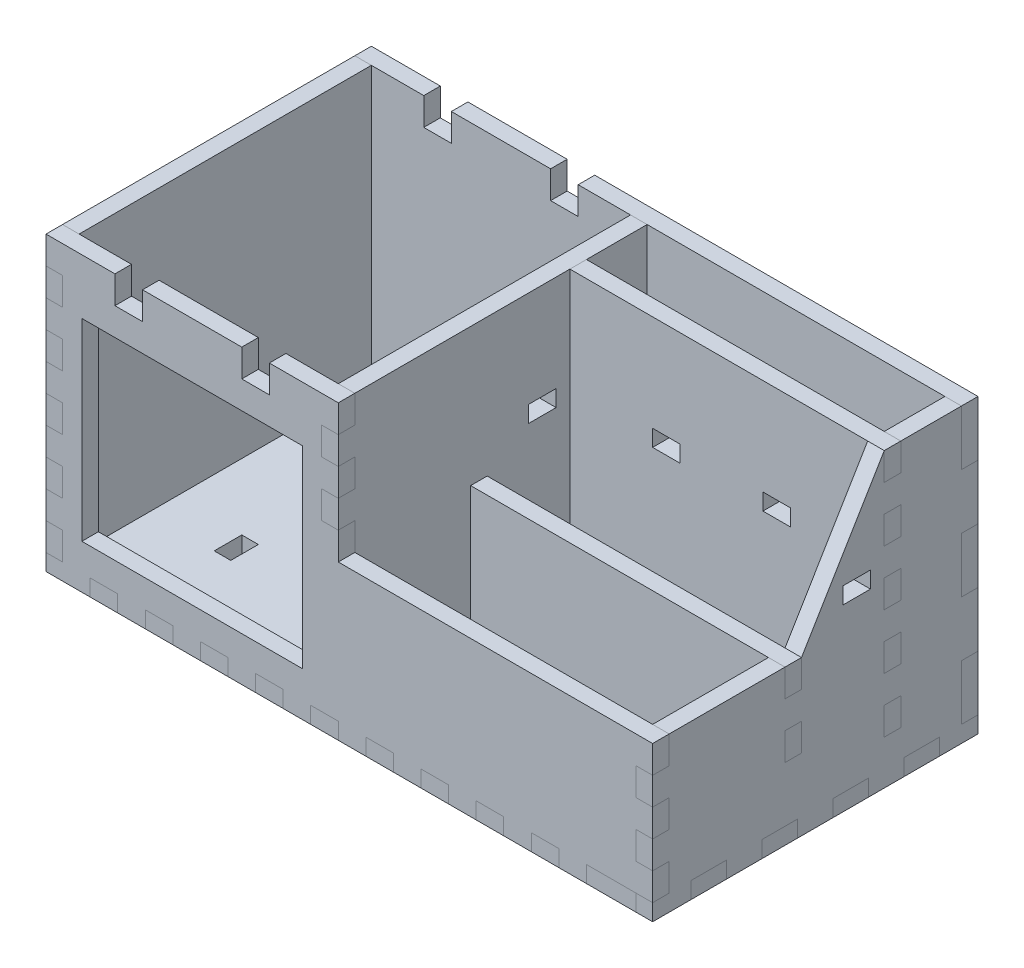
SolidWorks part; units mm, degrees
ref_plane "Front Plane" through (0, 0, 0) normal (0, 0, 1) x (1, 0, 0)
ref_plane "Top Plane" through (0, 0, 0) normal (0, 1, 0) x (1, 0, 0)
ref_plane "Right Plane" through (0, 0, 0) normal (1, 0, 0) x (0, 0, -1)
sketch "Sketch1" plane through (0, 0, 0) normal (0, 0, 1) x (1, 0, 0)
  line L0 (6, 106) -> (6, 0) construction
  line L1 (0, 0) -> (220, 0) construction
  line L2 (0, 0) -> (0, 106) construction
  line L3 (0, 106) -> (220, 106) construction
  line L4 (220, 0) -> (220, 106) construction
  line L5 (106, 106) -> (106, 0) construction
  line L6 (0, 6) -> (220, 6) construction
  line L7 (0, 56) -> (220, 56) construction
  line L8 (106, 106) -> (81, 106)
  line L9 (220, 56) -> (106, 56)
  line L10 (0, 106) -> (0, 96)
  line L11 (0, 96) -> (6, 96)
  line L12 (6, 96) -> (6, 86)
  line L13 (6, 86) -> (0, 86)
  line L14 (6, 66) -> (0, 66)
  line L15 (6, 76) -> (6, 66)
  line L16 (0, 76) -> (6, 76)
  line L17 (0, 86) -> (0, 76)
  line L18 (6, 46) -> (0, 46)
  line L19 (6, 56) -> (6, 46)
  line L20 (0, 56) -> (6, 56)
  line L21 (0, 66) -> (0, 56)
  line L22 (6, 26) -> (0, 26)
  line L23 (6, 36) -> (6, 26)
  line L24 (0, 36) -> (6, 36)
  line L25 (0, 46) -> (0, 36)
  line L26 (6, 6) -> (0, 6)
  line L27 (6, 16) -> (6, 6)
  line L28 (0, 16) -> (6, 16)
  line L29 (0, 26) -> (0, 16)
  line L30 (6, 0) -> (16, 0)
  line L31 (16, 0) -> (16, 6)
  line L32 (16, 6) -> (26, 6)
  line L33 (26, 6) -> (26, 0)
  line L34 (26, 0) -> (36, 0)
  line L35 (36, 0) -> (36, 6)
  line L36 (36, 6) -> (46, 6)
  line L37 (46, 6) -> (46, 0)
  line L38 (46, 0) -> (56, 0)
  line L39 (56, 0) -> (56, 6)
  line L40 (56, 6) -> (66, 6)
  line L41 (66, 6) -> (66, 0)
  line L42 (66, 0) -> (76, 0)
  line L43 (76, 0) -> (76, 6)
  line L44 (76, 6) -> (86, 6)
  line L45 (86, 6) -> (86, 0)
  line L46 (86, 0) -> (96, 0)
  line L47 (96, 0) -> (96, 6)
  line L48 (96, 6) -> (106, 6)
  line L49 (106, 6) -> (106, 0)
  line L50 (106, 0) -> (116, 0)
  line L51 (116, 0) -> (116, 6)
  line L52 (116, 6) -> (126, 6)
  line L53 (126, 6) -> (126, 0)
  line L54 (126, 0) -> (136, 0)
  line L55 (136, 0) -> (136, 6)
  line L56 (136, 6) -> (146, 6)
  line L57 (146, 6) -> (146, 0)
  line L58 (146, 0) -> (156, 0)
  line L59 (156, 0) -> (156, 6)
  line L60 (156, 6) -> (166, 6)
  line L61 (166, 6) -> (166, 0)
  line L62 (166, 0) -> (176, 0)
  line L63 (176, 0) -> (176, 6)
  line L64 (176, 6) -> (186, 6)
  line L65 (186, 6) -> (186, 0)
  line L66 (186, 0) -> (196, 0)
  line L67 (196, 0) -> (196, 6)
  line L68 (196, 6) -> (206, 6)
  line L69 (100, 106) -> (100, 6) construction
  line L70 (6, 0) -> (0, 0)
  line L71 (0, 0) -> (0, 6)
  line L72 (214, 56) -> (214, 0) construction
  line L73 (220, 56) -> (220, 46)
  line L74 (220, 46) -> (214, 46)
  line L75 (214, 46) -> (214, 36)
  line L76 (214, 36) -> (220, 36)
  line L77 (220, 36) -> (220, 26)
  line L78 (220, 26) -> (214, 26)
  line L79 (214, 26) -> (214, 16)
  line L80 (214, 16) -> (220, 16)
  line L81 (220, 16) -> (220, 6)
  line L82 (220, 6) -> (206, 6)
  line L83 (106, 106) -> (106, 96)
  line L84 (206, 6) -> (206, 0) [skipped]
  line L85 (106, 96) -> (100, 96)
  line L86 (100, 96) -> (100, 86)
  line L87 (100, 86) -> (106, 86)
  line L88 (106, 86) -> (106, 76)
  line L89 (106, 76) -> (100, 76)
  line L90 (100, 76) -> (100, 66)
  line L91 (100, 66) -> (106, 66)
  line L92 (106, 66) -> (106, 56)
  line L93 (25, 106) -> (0, 106)
  line L94 (35, 106) -> (25, 106) construction
  line L95 (71, 106) -> (35, 106)
  line L96 (81, 106) -> (71, 106) construction
  line L97 (0, 96) -> (106, 96) construction
  line L98 (25, 106) -> (25, 96)
  line L99 (25, 96) -> (35, 96)
  line L100 (35, 96) -> (35, 106)
  line L101 (71, 106) -> (71, 96)
  line L102 (71, 96) -> (81, 96)
  line L103 (81, 96) -> (81, 106)
  line L104 (53, 106) -> (53, 0) construction
  line L105 (13, 86) -> (93, 86)
  line L106 (13, 86) -> (13, 16)
  line L107 (13, 16) -> (93, 16)
  line L108 (93, 86) -> (93, 16)
  point P111 (53, 86)
  dimension "D1" = 6
  dimension "D2" = 220
  dimension "D3" = 106
  dimension "D4" = 6
  dimension "D5" = 106
  dimension "D6" = 56
  dimension "D7" = 10
  dimension "D10" = 6
  dimension "D11" = 6
  dimension "D12" = 10
  dimension "D13" = 10
  dimension "D14" = 25
  dimension "D15" = 25
  dimension "D16" = 10
  dimension "D17" = 70
  dimension "D18" = 10
  dimension "D19" = 80
  dimension "D8" = 5
  dimension "D9" = 10
extrude "Boss-Extrude1" add sketch "Sketch1" along normal blind 6
sketch "Sketch2" plane through (0, 0, 0) normal (0, 1, 0) x (1, 0, 0)
  line L0 (0, -6) -> (16, -6) construction
  line L1 (0, -6) -> (220, -6)
  line L2 (0, -6) -> (0, 112)
  line L3 (0, 112) -> (220, 112)
  line L4 (220, -6) -> (220, 112)
  line L5 (0, -6) -> (0, 0) construction
  dimension "D1" = 220
  dimension "D2" = 118
extrude "Boss-Extrude2" add sketch "Sketch2" along normal blind 6 separate body
sketch "Sketch5" plane through (0, 0, 0) normal (1, 0, 0) x (0, 0, -1)
  line L0 (-6, 26) -> (-6, 16) construction
  line L1 (-6, 106) -> (112, 106)
  line L2 (-6, 106) -> (-6, 6)
  line L3 (-6, 0) -> (112, 0) construction
  line L4 (112, 106) -> (112, 6)
  line L5 (112, 0) -> (-6, 0) construction
  line L6 (-6, 6) -> (0, 6)
  line L7 (0, 6) -> (0, 0)
  line L8 (0, 0) -> (11.7778, 0)
  line L9 (11.7778, 0) -> (11.7778, 6)
  line L10 (-6, 6) -> (112, 6) construction
  line L11 (11.7778, 6) -> (23.5556, 6)
  line L12 (23.5556, 6) -> (23.5556, 0)
  line L13 (23.5556, 0) -> (35.3333, 0)
  line L14 (35.3333, 0) -> (35.3333, 6)
  line L15 (35.3333, 6) -> (47.1111, 6)
  line L16 (47.1111, 6) -> (47.1111, 0)
  line L17 (47.1111, 0) -> (58.8889, 0)
  line L18 (58.8889, 0) -> (58.8889, 6)
  line L19 (58.8889, 6) -> (70.6667, 6)
  line L20 (70.6667, 6) -> (70.6667, 0)
  line L21 (70.6667, 0) -> (82.4444, 0)
  line L22 (82.4444, 0) -> (82.4444, 6)
  line L23 (82.4444, 6) -> (94.2222, 6)
  line L24 (94.2222, 6) -> (94.2222, 0)
  line L25 (94.2222, 0) -> (106, 0)
  line L26 (106, 0) -> (106, 6) construction
  line L27 (106, 6) -> (112, 6) construction
  line L28 (-6, 6) -> (-6, 0) construction
  line L29 (112, 6) -> (112, 0)
  line L30 (112, 0) -> (106, 0)
  dimension "D1" = 118
  dimension "D2" = 106
  dimension "D4" = 6
  dimension "D5" = 6
extrude "Boss-Extrude9" add sketch "Sketch5" along normal blind 6 separate body
sketch "Sketch11" plane through (214, 0, 0) normal (1, 0, 0) x (0, 0, -1)
  line L0 (-6, 0) -> (0, 0)
  line L1 (-6, 0) -> (112, 0) construction
  line L2 (-6, 0) -> (-6, 5.9466)
  line L3 (-6, 106) -> (78, 106) construction
  line L4 (112, 0) -> (112, 106)
  line L5 (0, 0) -> (8, 0)
  line L6 (98, 0) -> (112, 0)
  line L7 (8, 0) -> (8, 6)
  line L8 (8, 6) -> (20.8571, 6)
  line L9 (20.8571, 6) -> (20.8571, 0)
  line L10 (-6, 6) -> (112, 6) construction
  line L11 (0, 6) -> (0, 0) construction
  line L12 (-6, 5.9466) -> (-6, 56)
  line L13 (20.8571, 0) -> (33.7143, 0)
  line L14 (33.7143, 0) -> (33.7143, 6)
  line L15 (33.7143, 6) -> (46.5714, 6)
  line L16 (46.5714, 6) -> (46.5714, 0)
  line L17 (46.5714, 0) -> (59.4286, 0)
  line L18 (59.4286, 0) -> (59.4286, 6)
  line L19 (59.4286, 6) -> (72.2857, 6)
  line L20 (72.2857, 6) -> (72.2857, 0)
  line L21 (72.2857, 0) -> (85.1429, 0)
  line L22 (85.1429, 0) -> (85.1429, 6)
  line L23 (85.1429, 6) -> (98, 6)
  line L24 (98, 6) -> (98, 0)
  line L25 (-6, 46) -> (-6, 56) construction
  line L28 (-6, 56) -> (-6, 106) construction
  line L29 (78, 106) -> (112, 106)
  line L30 (78, 106) -> (48, 56)
  line L31 (-6, 56) -> (48, 56)
  line L32 (-6, 56) -> (0, 56) construction
  line L34 (112, 0) -> (112, 6) construction
  dimension "D1" = 106
  dimension "D2" = 118
  dimension "D3" = 6
  dimension "D4" = 8
  dimension "D5" = 14
  dimension "D6" = 34
  dimension "D7" = 54
extrude "Boss-Extrude11" add sketch "Sketch11" along normal blind 6 separate body
sketch "Sketch15" plane through (0, 0, -112) normal (0, 0, -1) x (-1, 0, 0)
  line L0 (-214, 106) -> (-214, 0) construction
  line L1 (-220, 0) -> (-214, 0) construction
  line L2 (-220, 0) -> (-220, 106) construction
  line L3 (-220, 106) -> (-81, 106)
  line L4 (0, 0) -> (0, 106) construction
  line L5 (-6, 106) -> (-6, 0) construction
  line L6 (-220, 106) -> (-220, 86)
  line L7 (-220, 86) -> (-214, 86)
  line L8 (-214, 86) -> (-214, 66)
  line L9 (-214, 66) -> (-220, 66)
  line L10 (-220, 66) -> (-220, 46)
  line L11 (-220, 46) -> (-214, 46)
  line L12 (-214, 46) -> (-214, 26)
  line L13 (-214, 26) -> (-220, 26)
  line L14 (-220, 26) -> (-220, 6)
  line L15 (-220, 6) -> (-214, 6) construction
  line L16 (-214, 6) -> (-214, 0)
  line L17 (-214, 0) -> (-6, 0) construction
  line L18 (-214, 6) -> (-220, 6)
  line L19 (0, 106) -> (0, 86)
  line L20 (0, 86) -> (-6, 86)
  line L21 (-6, 86) -> (-6, 66)
  line L22 (-6, 66) -> (0, 66)
  line L23 (0, 66) -> (0, 46)
  line L24 (0, 46) -> (-6, 46)
  line L25 (-6, 46) -> (-6, 26)
  line L26 (-6, 26) -> (0, 26)
  line L27 (0, 26) -> (0, 6)
  line L28 (0, 6) -> (-6, 6)
  line L29 (-6, 6) -> (-6, 0)
  line L30 (-6, 0) -> (0, 0) construction
  line L31 (-214, 0) -> (-195.0909, 0)
  line L32 (-195.0909, 0) -> (-195.0909, 6)
  line L33 (-220, 6) -> (0, 6) construction
  line L34 (-195.0909, 6) -> (-176.1818, 6)
  line L35 (-176.1818, 6) -> (-176.1818, 0)
  line L36 (-176.1818, 0) -> (-157.2727, 0)
  line L37 (-157.2727, 0) -> (-157.2727, 6)
  line L38 (-157.2727, 6) -> (-138.3636, 6)
  line L39 (-138.3636, 6) -> (-138.3636, 0)
  line L40 (-138.3636, 0) -> (-119.4545, 0)
  line L41 (-119.4545, 0) -> (-119.4545, 6)
  line L42 (-119.4545, 6) -> (-100.5455, 6)
  line L43 (-100.5455, 6) -> (-100.5455, 0)
  line L44 (-100.5455, 0) -> (-81.6364, 0)
  line L45 (-81.6364, 0) -> (-81.6364, 6)
  line L46 (-81.6364, 6) -> (-62.7273, 6)
  line L47 (-62.7273, 6) -> (-62.7273, 0)
  line L48 (-62.7273, 0) -> (-43.8182, 0)
  line L49 (-43.8182, 0) -> (-43.8182, 6)
  line L50 (-43.8182, 6) -> (-24.9091, 6)
  line L51 (-24.9091, 6) -> (-24.9091, 0)
  line L52 (-24.9091, 0) -> (-6, 0)
  line L53 (-81, 106) -> (-81, 96)
  line L54 (-81, 96) -> (-71, 96)
  line L55 (-81, 96) -> (-71, 96) construction
  line L56 (-71, 96) -> (-71, 106)
  line L57 (-81, 106) -> (-71, 106) construction
  line L58 (-71, 106) -> (-35, 106)
  line L59 (-35, 106) -> (-35, 96)
  line L60 (-35, 96) -> (-25, 96)
  line L61 (-25, 96) -> (-25, 106) construction
  line L62 (-35, 96) -> (-25, 96) construction
  line L63 (-25, 96) -> (-25, 106)
  line L64 (-35, 106) -> (-25, 106) construction
  line L65 (-25, 106) -> (0, 106)
  dimension "D1" = 220
  dimension "D2" = 106
  dimension "D3" = 6
  dimension "D4" = 6
  dimension "D5" = 6
extrude "Boss-Extrude13" add sketch "Sketch15" against normal blind 6 separate body
sketch "Sketch22" plane through (100, 0, 0) normal (1, 0, 0) x (0, 0, -1)
  line L0 (-6, 86) -> (-6, 96) construction
  line L1 (-6, 106) -> (106, 106)
  line L2 (-6, 106) -> (-6, 6)
  line L3 (-6, 6) -> (19, 6)
  line L4 (112, 106) -> (112, 6) construction
  line L5 (106, 106) -> (112, 106) construction
  line L6 (106, 106) -> (106, 6) construction
  line L7 (106, 106) -> (106, 86)
  line L8 (106, 86) -> (112, 86)
  line L9 (112, 86) -> (112, 66)
  line L10 (112, 66) -> (106, 66)
  line L11 (106, 66) -> (106, 46)
  line L12 (106, 46) -> (112, 46)
  line L13 (112, 46) -> (112, 26)
  line L14 (112, 26) -> (106, 26)
  line L15 (106, 26) -> (106, 6)
  line L16 (106, 6) -> (112, 6) construction
  line L17 (-6, 0) -> (94, 0) construction
  line L18 (19, 6) -> (34, 6) construction
  line L19 (34, 6) -> (59, 6)
  line L20 (59, 6) -> (74, 6) construction
  line L21 (74, 6) -> (106, 6)
  line L22 (19, 6) -> (19, 0)
  line L23 (19, 0) -> (34, 0)
  line L24 (34, 0) -> (34, 6)
  line L25 (59, 6) -> (59, 0)
  line L26 (59, 0) -> (74, 0)
  line L27 (74, 0) -> (74, 6)
  dimension "D1" = 118
  dimension "D2" = 100
  dimension "D3" = 6
  dimension "D4" = 15
  dimension "D5" = 25
  dimension "D6" = 25
extrude "Boss-Extrude14" add sketch "Sketch22" along normal blind 6 separate body
sketch "Sketch19" plane through (0, 0, -112) normal (0, 0, -1) x (-1, 0, 0)
  line L44 (0, 86) -> (0, 106)
  line L45 (-81, 106) -> (-220, 106)
  line L46 (-220, 106) -> (-220, 86)
  line L47 (-220, 86) -> (-214, 86)
  line L48 (-214, 86) -> (-214, 66)
  line L49 (-214, 66) -> (-220, 66)
  line L50 (-220, 66) -> (-220, 46)
  line L51 (-220, 46) -> (-214, 46)
  line L52 (-214, 46) -> (-214, 26)
  line L53 (-214, 26) -> (-220, 26)
  line L54 (-220, 26) -> (-220, 6)
  line L55 (-220, 6) -> (-214, 6)
  line L56 (-214, 6) -> (-214, 0)
  line L57 (-214, 0) -> (-195.0909, 0)
  line L58 (-195.0909, 0) -> (-195.0909, 6)
  line L59 (-195.0909, 6) -> (-176.1818, 6)
  line L60 (-176.1818, 6) -> (-176.1818, 0)
  line L61 (-176.1818, 0) -> (-157.2727, 0)
  line L62 (-157.2727, 0) -> (-157.2727, 6)
  line L63 (-157.2727, 6) -> (-138.3636, 6)
  line L64 (-138.3636, 6) -> (-138.3636, 0)
  line L65 (-138.3636, 0) -> (-119.4545, 0)
  line L66 (-119.4545, 0) -> (-119.4545, 6)
  line L67 (-119.4545, 6) -> (-100.5455, 6)
  line L68 (-100.5455, 6) -> (-100.5455, 0)
  line L69 (-100.5455, 0) -> (-81.6364, 0)
  line L70 (-81.6364, 0) -> (-81.6364, 6)
  line L71 (-81.6364, 6) -> (-62.7273, 6)
  line L72 (-62.7273, 6) -> (-62.7273, 0)
  line L73 (-62.7273, 0) -> (-43.8182, 0)
  line L74 (-43.8182, 0) -> (-43.8182, 6)
  line L75 (-43.8182, 6) -> (-24.9091, 6)
  line L76 (-24.9091, 6) -> (-24.9091, 0)
  line L77 (-24.9091, 0) -> (-6, 0)
  line L78 (-6, 0) -> (-6, 6)
  line L79 (-6, 6) -> (0, 6)
  line L80 (0, 6) -> (0, 26)
  line L81 (0, 26) -> (-6, 26)
  line L82 (-6, 26) -> (-6, 46)
  line L83 (-6, 46) -> (0, 46)
  line L84 (0, 46) -> (0, 66)
  line L85 (0, 66) -> (-6, 66)
  line L86 (-6, 66) -> (-6, 86)
  line L87 (-6, 86) -> (0, 86)
  line L88 (0, 86) -> (0, 106)
  line L89 (-81, 106) -> (-220, 106)
  line L90 (-220, 106) -> (-220, 86)
  line L91 (-220, 86) -> (-214, 86)
  line L92 (-214, 86) -> (-214, 66)
  line L93 (-214, 66) -> (-220, 66)
  line L94 (-220, 66) -> (-220, 46)
  line L95 (-220, 46) -> (-214, 46)
  line L96 (-214, 46) -> (-214, 26)
  line L97 (-214, 26) -> (-220, 26)
  line L98 (-220, 26) -> (-220, 6)
  line L99 (-220, 6) -> (-214, 6)
  line L100 (-214, 6) -> (-214, 0)
  line L101 (-214, 0) -> (-195.0909, 0)
  line L102 (-195.0909, 0) -> (-195.0909, 6)
  line L103 (-195.0909, 6) -> (-176.1818, 6)
  line L104 (-176.1818, 6) -> (-176.1818, 0)
  line L105 (-176.1818, 0) -> (-157.2727, 0)
  line L106 (-157.2727, 0) -> (-157.2727, 6)
  line L107 (-157.2727, 6) -> (-138.3636, 6)
  line L108 (-138.3636, 6) -> (-138.3636, 0)
  line L109 (-138.3636, 0) -> (-119.4545, 0)
  line L110 (-119.4545, 0) -> (-119.4545, 6)
  line L111 (-119.4545, 6) -> (-100.5455, 6)
  line L112 (-100.5455, 6) -> (-100.5455, 0)
  line L113 (-100.5455, 0) -> (-81.6364, 0)
  line L114 (-81.6364, 0) -> (-81.6364, 6)
  line L115 (-81.6364, 6) -> (-62.7273, 6)
  line L116 (-62.7273, 6) -> (-62.7273, 0)
  line L117 (-62.7273, 0) -> (-43.8182, 0)
  line L118 (-43.8182, 0) -> (-43.8182, 6)
  line L119 (-43.8182, 6) -> (-24.9091, 6)
  line L120 (-24.9091, 6) -> (-24.9091, 0)
  line L121 (-24.9091, 0) -> (-6, 0)
  line L122 (-6, 0) -> (-6, 6)
  line L123 (-6, 6) -> (0, 6)
  line L124 (0, 6) -> (0, 26)
  line L125 (0, 26) -> (-6, 26)
  line L126 (-6, 26) -> (-6, 46)
  line L127 (-6, 46) -> (0, 46)
  line L128 (0, 46) -> (0, 66)
  line L129 (0, 66) -> (-6, 66)
  line L130 (-6, 66) -> (-6, 86)
  line L131 (-6, 86) -> (0, 86)
  line L140 (0, 106) -> (-25, 106)
  line L141 (0, 106) -> (-25, 106)
  line L142 (-25, 106) -> (-25, 96)
  line L143 (-25, 106) -> (-25, 96)
  line L144 (-25, 96) -> (-35, 96)
  line L145 (-25, 96) -> (-35, 96)
  line L146 (-35, 96) -> (-35, 106)
  line L147 (-35, 96) -> (-35, 106)
  line L148 (-35, 106) -> (-71, 106)
  line L149 (-35, 106) -> (-71, 106)
  line L150 (-71, 106) -> (-71, 96)
  line L151 (-71, 106) -> (-71, 96)
  line L152 (-71, 96) -> (-81, 96)
  line L153 (-71, 96) -> (-81, 96)
  line L154 (-81, 96) -> (-81, 106)
  line L155 (-81, 96) -> (-81, 106)
  dimension "D1" = 0
extrude "Cut-Extrude2" cut sketch "Sketch19" against normal blind 6
sketch "Sketch13" plane through (0, 0, 6) normal (0, 0, 1) x (1, 0, 0)
  line L80 (0, 6) -> (0, 0)
  line L81 (0, 0) -> (16, 0)
  line L82 (16, 0) -> (16, 6)
  line L83 (16, 6) -> (26, 6)
  line L84 (26, 6) -> (26, 0)
  line L85 (26, 0) -> (36, 0)
  line L86 (36, 0) -> (36, 6)
  line L87 (36, 6) -> (46, 6)
  line L88 (46, 6) -> (46, 0)
  line L89 (46, 0) -> (56, 0)
  line L90 (56, 0) -> (56, 6)
  line L91 (56, 6) -> (66, 6)
  line L92 (66, 6) -> (66, 0)
  line L93 (66, 0) -> (76, 0)
  line L94 (76, 0) -> (76, 6)
  line L95 (76, 6) -> (86, 6)
  line L96 (86, 6) -> (86, 0)
  line L97 (86, 0) -> (96, 0)
  line L98 (96, 0) -> (96, 6)
  line L99 (96, 6) -> (106, 6)
  line L100 (106, 6) -> (106, 0)
  line L101 (106, 0) -> (116, 0)
  line L102 (116, 0) -> (116, 6)
  line L103 (116, 6) -> (126, 6)
  line L104 (126, 6) -> (126, 0)
  line L105 (126, 0) -> (136, 0)
  line L106 (136, 0) -> (136, 6)
  line L107 (136, 6) -> (146, 6)
  line L108 (146, 6) -> (146, 0)
  line L109 (146, 0) -> (156, 0)
  line L110 (156, 0) -> (156, 6)
  line L111 (156, 6) -> (166, 6)
  line L112 (166, 6) -> (166, 0)
  line L113 (166, 0) -> (176, 0)
  line L114 (176, 0) -> (176, 6)
  line L115 (176, 6) -> (186, 6)
  line L116 (186, 6) -> (186, 0)
  line L117 (186, 0) -> (196, 0)
  line L118 (196, 0) -> (196, 6)
  line L119 (196, 6) -> (220, 6)
  line L120 (220, 6) -> (220, 16)
  line L121 (220, 16) -> (214, 16)
  line L122 (214, 16) -> (214, 26)
  line L123 (214, 26) -> (220, 26)
  line L124 (220, 26) -> (220, 36)
  line L125 (220, 36) -> (214, 36)
  line L126 (214, 36) -> (214, 46)
  line L127 (214, 46) -> (220, 46)
  line L128 (220, 46) -> (220, 56)
  line L129 (220, 56) -> (106, 56)
  line L130 (106, 56) -> (106, 66)
  line L131 (106, 66) -> (100, 66)
  line L132 (100, 66) -> (100, 76)
  line L133 (100, 76) -> (106, 76)
  line L134 (106, 76) -> (106, 86)
  line L135 (106, 86) -> (100, 86)
  line L136 (100, 86) -> (100, 96)
  line L137 (100, 96) -> (106, 96)
  line L138 (106, 96) -> (106, 106)
  line L139 (106, 106) -> (81, 106)
  line L140 (0, 106) -> (0, 96)
  line L141 (0, 96) -> (6, 96)
  line L142 (6, 96) -> (6, 86)
  line L143 (6, 86) -> (0, 86)
  line L144 (0, 86) -> (0, 76)
  line L145 (0, 76) -> (6, 76)
  line L146 (6, 76) -> (6, 66)
  line L147 (6, 66) -> (0, 66)
  line L148 (0, 66) -> (0, 56)
  line L149 (0, 56) -> (6, 56)
  line L150 (6, 56) -> (6, 46)
  line L151 (6, 46) -> (0, 46)
  line L152 (0, 46) -> (0, 36)
  line L153 (0, 36) -> (6, 36)
  line L154 (6, 36) -> (6, 26)
  line L155 (6, 26) -> (0, 26)
  line L156 (0, 26) -> (0, 16)
  line L157 (0, 16) -> (6, 16)
  line L158 (6, 16) -> (6, 6)
  line L159 (6, 6) -> (0, 6)
  line L160 (0, 6) -> (0, 0)
  line L161 (0, 0) -> (16, 0)
  line L162 (16, 0) -> (16, 6)
  line L163 (16, 6) -> (26, 6)
  line L164 (26, 6) -> (26, 0)
  line L165 (26, 0) -> (36, 0)
  line L166 (36, 0) -> (36, 6)
  line L167 (36, 6) -> (46, 6)
  line L168 (46, 6) -> (46, 0)
  line L169 (46, 0) -> (56, 0)
  line L170 (56, 0) -> (56, 6)
  line L171 (56, 6) -> (66, 6)
  line L172 (66, 6) -> (66, 0)
  line L173 (66, 0) -> (76, 0)
  line L174 (76, 0) -> (76, 6)
  line L175 (76, 6) -> (86, 6)
  line L176 (86, 6) -> (86, 0)
  line L177 (86, 0) -> (96, 0)
  line L178 (96, 0) -> (96, 6)
  line L179 (96, 6) -> (106, 6)
  line L180 (106, 6) -> (106, 0)
  line L181 (106, 0) -> (116, 0)
  line L182 (116, 0) -> (116, 6)
  line L183 (116, 6) -> (126, 6)
  line L184 (126, 6) -> (126, 0)
  line L185 (126, 0) -> (136, 0)
  line L186 (136, 0) -> (136, 6)
  line L187 (136, 6) -> (146, 6)
  line L188 (146, 6) -> (146, 0)
  line L189 (146, 0) -> (156, 0)
  line L190 (156, 0) -> (156, 6)
  line L191 (156, 6) -> (166, 6)
  line L192 (166, 6) -> (166, 0)
  line L193 (166, 0) -> (176, 0)
  line L194 (176, 0) -> (176, 6)
  line L195 (176, 6) -> (186, 6)
  line L196 (186, 6) -> (186, 0)
  line L197 (186, 0) -> (196, 0)
  line L198 (196, 0) -> (196, 6)
  line L199 (196, 6) -> (220, 6)
  line L200 (220, 6) -> (220, 16)
  line L201 (220, 16) -> (214, 16)
  line L202 (214, 16) -> (214, 26)
  line L203 (214, 26) -> (220, 26)
  line L204 (220, 26) -> (220, 36)
  line L205 (220, 36) -> (214, 36)
  line L206 (214, 36) -> (214, 46)
  line L207 (214, 46) -> (220, 46)
  line L208 (220, 46) -> (220, 56)
  line L209 (220, 56) -> (106, 56)
  line L210 (106, 56) -> (106, 66)
  line L211 (106, 66) -> (100, 66)
  line L212 (100, 66) -> (100, 76)
  line L213 (100, 76) -> (106, 76)
  line L214 (106, 76) -> (106, 86)
  line L215 (106, 86) -> (100, 86)
  line L216 (100, 86) -> (100, 96)
  line L217 (100, 96) -> (106, 96)
  line L218 (106, 96) -> (106, 106)
  line L219 (106, 106) -> (81, 106)
  line L220 (0, 106) -> (0, 96)
  line L221 (0, 96) -> (6, 96)
  line L222 (6, 96) -> (6, 86)
  line L223 (6, 86) -> (0, 86)
  line L224 (0, 86) -> (0, 76)
  line L225 (0, 76) -> (6, 76)
  line L226 (6, 76) -> (6, 66)
  line L227 (6, 66) -> (0, 66)
  line L228 (0, 66) -> (0, 56)
  line L229 (0, 56) -> (6, 56)
  line L230 (6, 56) -> (6, 46)
  line L231 (6, 46) -> (0, 46)
  line L232 (0, 46) -> (0, 36)
  line L233 (0, 36) -> (6, 36)
  line L234 (6, 36) -> (6, 26)
  line L235 (6, 26) -> (0, 26)
  line L236 (0, 26) -> (0, 16)
  line L237 (0, 16) -> (6, 16)
  line L238 (6, 16) -> (6, 6)
  line L239 (6, 6) -> (0, 6)
  line L248 (81, 106) -> (81, 96)
  line L249 (81, 106) -> (81, 96)
  line L250 (81, 96) -> (71, 96)
  line L251 (81, 96) -> (71, 96)
  line L252 (71, 96) -> (71, 106)
  line L253 (71, 96) -> (71, 106)
  line L254 (71, 106) -> (35, 106)
  line L255 (71, 106) -> (35, 106)
  line L256 (35, 106) -> (35, 96)
  line L257 (35, 106) -> (35, 96)
  line L258 (35, 96) -> (25, 96)
  line L259 (35, 96) -> (25, 96)
  line L260 (25, 96) -> (25, 106)
  line L261 (25, 96) -> (25, 106)
  line L262 (25, 106) -> (0, 106)
  line L263 (25, 106) -> (0, 106)
  dimension "D1" = 0
extrude "Cut-Extrude1" cut sketch "Sketch13" against normal blind 6
sketch "Sketch20" plane through (0, 0, 0) normal (-1, 0, 0) x (0, 0, 1)
  line L48 (-112, 46) -> (-112, 26)
  line L51 (-112, 0) -> (-94.2222, 0)
  line L52 (-94.2222, 0) -> (-94.2222, 6)
  line L53 (-94.2222, 6) -> (-82.4444, 6)
  line L54 (-82.4444, 6) -> (-82.4444, 0)
  line L55 (-82.4444, 0) -> (-70.6667, 0)
  line L56 (-70.6667, 0) -> (-70.6667, 6)
  line L57 (-70.6667, 6) -> (-58.8889, 6)
  line L58 (-58.8889, 6) -> (-58.8889, 0)
  line L59 (-58.8889, 0) -> (-47.1111, 0)
  line L60 (-47.1111, 0) -> (-47.1111, 6)
  line L61 (-47.1111, 6) -> (-35.3333, 6)
  line L62 (-35.3333, 6) -> (-35.3333, 0)
  line L63 (-35.3333, 0) -> (-23.5556, 0)
  line L64 (-23.5556, 0) -> (-23.5556, 6)
  line L65 (-23.5556, 6) -> (-11.7778, 6)
  line L66 (-11.7778, 6) -> (-11.7778, 0)
  line L67 (-11.7778, 0) -> (0, 0)
  line L68 (0, 0) -> (0, 6)
  line L69 (0, 6) -> (6, 6)
  line L70 (6, 6) -> (6, 16)
  line L71 (6, 16) -> (0, 16)
  line L72 (0, 16) -> (0, 26)
  line L73 (0, 26) -> (6, 26)
  line L74 (6, 26) -> (6, 36)
  line L75 (6, 36) -> (0, 36)
  line L76 (0, 36) -> (0, 46)
  line L77 (0, 46) -> (6, 46)
  line L78 (6, 46) -> (6, 56)
  line L79 (6, 56) -> (0, 56)
  line L80 (0, 56) -> (0, 66)
  line L81 (0, 66) -> (6, 66)
  line L82 (6, 66) -> (6, 76)
  line L83 (6, 76) -> (0, 76)
  line L84 (0, 76) -> (0, 86)
  line L85 (0, 86) -> (6, 86)
  line L86 (6, 86) -> (6, 96)
  line L87 (6, 96) -> (0, 96)
  line L88 (0, 96) -> (0, 106)
  line L89 (0, 106) -> (-106, 106)
  line L90 (-112, 26) -> (-106, 26)
  line L91 (-112, 26) -> (-106, 26)
  line L92 (-106, 106) -> (-106, 86)
  line L93 (-106, 106) -> (-106, 86)
  line L94 (-106, 86) -> (-112, 86)
  line L95 (-106, 86) -> (-112, 86)
  line L96 (-112, 46) -> (-112, 26)
  line L97 (-112, 86) -> (-112, 66)
  line L98 (-112, 86) -> (-112, 66)
  line L99 (-112, 0) -> (-94.2222, 0)
  line L100 (-94.2222, 0) -> (-94.2222, 6)
  line L101 (-94.2222, 6) -> (-82.4444, 6)
  line L102 (-82.4444, 6) -> (-82.4444, 0)
  line L103 (-82.4444, 0) -> (-70.6667, 0)
  line L104 (-70.6667, 0) -> (-70.6667, 6)
  line L105 (-70.6667, 6) -> (-58.8889, 6)
  line L106 (-58.8889, 6) -> (-58.8889, 0)
  line L107 (-58.8889, 0) -> (-47.1111, 0)
  line L108 (-47.1111, 0) -> (-47.1111, 6)
  line L109 (-47.1111, 6) -> (-35.3333, 6)
  line L110 (-35.3333, 6) -> (-35.3333, 0)
  line L111 (-35.3333, 0) -> (-23.5556, 0)
  line L112 (-23.5556, 0) -> (-23.5556, 6)
  line L113 (-23.5556, 6) -> (-11.7778, 6)
  line L114 (-11.7778, 6) -> (-11.7778, 0)
  line L115 (-11.7778, 0) -> (0, 0)
  line L116 (0, 0) -> (0, 6)
  line L117 (0, 6) -> (6, 6)
  line L118 (6, 6) -> (6, 16)
  line L119 (6, 16) -> (0, 16)
  line L120 (0, 16) -> (0, 26)
  line L121 (0, 26) -> (6, 26)
  line L122 (6, 26) -> (6, 36)
  line L123 (6, 36) -> (0, 36)
  line L124 (0, 36) -> (0, 46)
  line L125 (0, 46) -> (6, 46)
  line L126 (6, 46) -> (6, 56)
  line L127 (6, 56) -> (0, 56)
  line L128 (0, 56) -> (0, 66)
  line L129 (0, 66) -> (6, 66)
  line L130 (6, 66) -> (6, 76)
  line L131 (6, 76) -> (0, 76)
  line L132 (0, 76) -> (0, 86)
  line L133 (0, 86) -> (6, 86)
  line L134 (6, 86) -> (6, 96)
  line L135 (6, 96) -> (0, 96)
  line L136 (0, 96) -> (0, 106)
  line L137 (0, 106) -> (-106, 106)
  line L138 (-112, 66) -> (-106, 66)
  line L139 (-112, 66) -> (-106, 66)
  line L140 (-106, 66) -> (-106, 46)
  line L141 (-106, 66) -> (-106, 46)
  line L142 (-106, 46) -> (-112, 46)
  line L143 (-106, 46) -> (-112, 46)
  line L144 (-106, 26) -> (-106, 6)
  line L145 (-106, 26) -> (-106, 6)
  line L146 (-106, 6) -> (-112, 6)
  line L147 (-106, 6) -> (-112, 6)
  line L148 (-112, 6) -> (-112, 0)
  line L149 (-112, 6) -> (-112, 0)
  dimension "D1" = 0
extrude "Cut-Extrude4" cut sketch "Sketch20" against normal blind 6
sketch "Sketch21" plane through (220, 0, 0) normal (1, 0, 0) x (0, 0, -1)
  line L42 (112, 66) -> (112, 86)
  line L43 (112, 86) -> (106, 86)
  line L44 (112, 86) -> (106, 86)
  line L45 (106, 106) -> (78, 106)
  line L46 (78, 106) -> (48, 56)
  line L47 (48, 56) -> (0, 56)
  line L48 (0, 56) -> (0, 46)
  line L49 (0, 46) -> (-6, 46)
  line L50 (-6, 46) -> (-6, 36)
  line L51 (-6, 36) -> (0, 36)
  line L52 (0, 36) -> (0, 26)
  line L53 (0, 26) -> (-6, 26)
  line L54 (-6, 26) -> (-6, 16)
  line L55 (-6, 16) -> (0, 16)
  line L56 (0, 16) -> (0, 6)
  line L57 (0, 6) -> (-6, 6)
  line L58 (-6, 6) -> (-6, 0)
  line L59 (-6, 0) -> (8, 0)
  line L60 (8, 0) -> (8, 6)
  line L61 (8, 6) -> (20.8571, 6)
  line L62 (20.8571, 6) -> (20.8571, 0)
  line L63 (20.8571, 0) -> (33.7143, 0)
  line L64 (33.7143, 0) -> (33.7143, 6)
  line L65 (33.7143, 6) -> (46.5714, 6)
  line L66 (46.5714, 6) -> (46.5714, 0)
  line L67 (46.5714, 0) -> (59.4286, 0)
  line L68 (59.4286, 0) -> (59.4286, 6)
  line L69 (59.4286, 6) -> (72.2857, 6)
  line L70 (72.2857, 6) -> (72.2857, 0)
  line L71 (72.2857, 0) -> (85.1429, 0)
  line L72 (85.1429, 0) -> (85.1429, 6)
  line L73 (85.1429, 6) -> (98, 6)
  line L74 (98, 6) -> (98, 0)
  line L75 (98, 0) -> (112, 0)
  line L76 (106, 86) -> (106, 106)
  line L77 (106, 86) -> (106, 106)
  line L78 (112, 0) -> (112, 6)
  line L79 (112, 0) -> (112, 6)
  line L80 (112, 6) -> (106, 6)
  line L81 (112, 6) -> (106, 6)
  line L82 (106, 6) -> (106, 26)
  line L83 (106, 6) -> (106, 26)
  line L84 (112, 66) -> (112, 86)
  line L85 (106, 26) -> (112, 26)
  line L86 (106, 26) -> (112, 26)
  line L87 (106, 106) -> (78, 106)
  line L88 (78, 106) -> (48, 56)
  line L89 (48, 56) -> (0, 56)
  line L90 (0, 56) -> (0, 46)
  line L91 (0, 46) -> (-6, 46)
  line L92 (-6, 46) -> (-6, 36)
  line L93 (-6, 36) -> (0, 36)
  line L94 (0, 36) -> (0, 26)
  line L95 (0, 26) -> (-6, 26)
  line L96 (-6, 26) -> (-6, 16)
  line L97 (-6, 16) -> (0, 16)
  line L98 (0, 16) -> (0, 6)
  line L99 (0, 6) -> (-6, 6)
  line L100 (-6, 6) -> (-6, 0)
  line L101 (-6, 0) -> (8, 0)
  line L102 (8, 0) -> (8, 6)
  line L103 (8, 6) -> (20.8571, 6)
  line L104 (20.8571, 6) -> (20.8571, 0)
  line L105 (20.8571, 0) -> (33.7143, 0)
  line L106 (33.7143, 0) -> (33.7143, 6)
  line L107 (33.7143, 6) -> (46.5714, 6)
  line L108 (46.5714, 6) -> (46.5714, 0)
  line L109 (46.5714, 0) -> (59.4286, 0)
  line L110 (59.4286, 0) -> (59.4286, 6)
  line L111 (59.4286, 6) -> (72.2857, 6)
  line L112 (72.2857, 6) -> (72.2857, 0)
  line L113 (72.2857, 0) -> (85.1429, 0)
  line L114 (85.1429, 0) -> (85.1429, 6)
  line L115 (85.1429, 6) -> (98, 6)
  line L116 (98, 6) -> (98, 0)
  line L117 (98, 0) -> (112, 0)
  line L118 (112, 26) -> (112, 46)
  line L119 (112, 26) -> (112, 46)
  line L120 (112, 46) -> (106, 46)
  line L121 (112, 46) -> (106, 46)
  line L122 (106, 46) -> (106, 66)
  line L123 (106, 46) -> (106, 66)
  line L124 (106, 66) -> (112, 66)
  line L125 (106, 66) -> (112, 66)
  dimension "D1" = 0
extrude "Cut-Extrude5" cut sketch "Sketch21" against normal blind 6
sketch "Sketch23" plane through (106, 0, 0) normal (1, 0, 0) x (0, 0, -1)
  line L28 (0, 96) -> (-6, 96)
  line L29 (-6, 96) -> (-6, 86)
  line L30 (-6, 86) -> (0, 86)
  line L31 (0, 86) -> (0, 76)
  line L32 (0, 76) -> (-6, 76)
  line L33 (-6, 76) -> (-6, 66)
  line L34 (-6, 66) -> (0, 66)
  line L35 (0, 66) -> (0, 6)
  line L36 (0, 6) -> (19, 6)
  line L37 (19, 6) -> (19, 0)
  line L38 (19, 0) -> (34, 0)
  line L39 (34, 0) -> (34, 6)
  line L40 (34, 6) -> (59, 6)
  line L41 (59, 6) -> (59, 0)
  line L42 (59, 0) -> (74, 0)
  line L43 (74, 0) -> (74, 6)
  line L44 (74, 6) -> (106, 6)
  line L45 (106, 6) -> (106, 26)
  line L46 (106, 26) -> (112, 26)
  line L47 (112, 26) -> (112, 46)
  line L48 (112, 46) -> (106, 46)
  line L49 (106, 46) -> (106, 66)
  line L50 (106, 66) -> (112, 66)
  line L51 (112, 66) -> (112, 86)
  line L52 (112, 86) -> (106, 86)
  line L53 (106, 86) -> (106, 106)
  line L54 (106, 106) -> (0, 106)
  line L55 (0, 106) -> (0, 96)
  line L56 (0, 96) -> (-6, 96)
  line L57 (-6, 96) -> (-6, 86)
  line L58 (-6, 86) -> (0, 86)
  line L59 (0, 86) -> (0, 76)
  line L60 (0, 76) -> (-6, 76)
  line L61 (-6, 76) -> (-6, 66)
  line L62 (-6, 66) -> (0, 66)
  line L63 (0, 66) -> (0, 6)
  line L64 (0, 6) -> (19, 6)
  line L65 (19, 6) -> (19, 0)
  line L66 (19, 0) -> (34, 0)
  line L67 (34, 0) -> (34, 6)
  line L68 (34, 6) -> (59, 6)
  line L69 (59, 6) -> (59, 0)
  line L70 (59, 0) -> (74, 0)
  line L71 (74, 0) -> (74, 6)
  line L72 (74, 6) -> (106, 6)
  line L73 (106, 6) -> (106, 26)
  line L74 (106, 26) -> (112, 26)
  line L75 (112, 26) -> (112, 46)
  line L76 (112, 46) -> (106, 46)
  line L77 (106, 46) -> (106, 66)
  line L78 (106, 66) -> (112, 66)
  line L79 (112, 66) -> (112, 86)
  line L80 (112, 86) -> (106, 86)
  line L81 (106, 86) -> (106, 106)
  line L82 (106, 106) -> (0, 106)
  line L83 (0, 106) -> (0, 96)
  dimension "D1" = 0
extrude "Cut-Extrude6" cut sketch "Sketch23" against normal blind 6
sketch "Sketch26" plane through (0, 6, 0) normal (0, 1, 0) x (1, 0, 0)
  line L0 (106, 74) -> (106, 106) construction
  line L1 (106, 84) -> (214, 84)
  line L2 (106, 84) -> (106, 78)
  line L3 (106, 78) -> (214, 78)
  line L4 (214, 84) -> (214, 78)
  line L5 (214, 59.4286) -> (214, 72.2857) construction
  line L6 (81, 112) -> (220, 112) construction
  dimension "D1" = 6
  dimension "D2" = 28
extrude "Boss-Extrude16" add sketch "Sketch26" along normal blind 100 separate body
sketch "Sketch28" plane through (214, 0, 0) normal (1, 0, 0) x (0, 0, -1)
  line L1 (78, 86) -> (84, 86)
  line L2 (78, 86) -> (78, 76)
  line L3 (78, 76) -> (84, 76)
  line L4 (84, 86) -> (84, 76)
  line L5 (84, 106) -> (84, 6) construction
  line L6 (78, 66) -> (84, 66)
  line L7 (78, 106) -> (84, 106)
  line L8 (78, 106) -> (78, 96)
  line L9 (78, 96) -> (84, 96)
  line L10 (84, 106) -> (84, 96)
  line L11 (78, 66) -> (78, 56)
  line L12 (78, 56) -> (84, 56)
  line L13 (84, 66) -> (84, 56)
  line L14 (78, 46) -> (84, 46)
  line L15 (78, 46) -> (78, 36)
  line L16 (78, 36) -> (84, 36)
  line L17 (84, 46) -> (84, 36)
  line L18 (78, 26) -> (84, 26)
  line L19 (78, 26) -> (78, 16)
  line L20 (78, 16) -> (84, 16)
  line L21 (84, 26) -> (84, 16)
  dimension "D1" = 10
  dimension "D2" = 5
extrude "Boss-Extrude17" add sketch "Sketch28" along normal blind 6 separate body
combine bodies "Combine1" operation type add bodies to combine 147 172 175 176 177 178
sketch "Sketch29" plane through (106, 0, 0) normal (-1, 0, 0) x (0, 0, 1)
  line L0 (-84, 106) -> (-84, 6) construction
  line L1 (-84, 48.9758) -> (-78, 48.9758)
  line L2 (-84, 48.9758) -> (-84, 28.9758)
  line L3 (-84, 28.9758) -> (-78, 28.9758)
  line L4 (-78, 48.9758) -> (-78, 28.9758)
  line L5 (-78, 106) -> (-78, 6) construction
  line L7 (-84, 72.8816) -> (-78, 72.8816)
  line L8 (-84, 72.8816) -> (-84, 92.8816)
  line L9 (-84, 92.8816) -> (-78, 92.8816)
  line L10 (-78, 72.8816) -> (-78, 92.8816)
  dimension "D1" = 20
extrude "Boss-Extrude18" add sketch "Sketch29" along normal blind 6 separate body
sketch "Sketch32" plane through (0, 6, 0) normal (0, -1, 0) x (1, 0, 0)
  line L0 (106, -78) -> (214, -78) construction
  line L1 (189.1666, -78) -> (169.1666, -78)
  line L2 (189.1666, -78) -> (189.1666, -84)
  line L3 (189.1666, -84) -> (169.1666, -84)
  line L4 (169.1666, -78) -> (169.1666, -84)
  line L5 (149.1666, -84) -> (129.1666, -84)
  line L6 (149.1666, -84) -> (149.1666, -78)
  line L7 (149.1666, -78) -> (129.1666, -78)
  line L8 (129.1666, -84) -> (129.1666, -78)
  dimension "D1" = 20
  dimension "D2" = 20
  dimension "D3" = 6
extrude "Boss-Extrude19" add sketch "Sketch32" along normal blind 6 separate body
combine bodies "Combine3" operation type add bodies to combine 155 154 149 150
sketch "Sketch34" plane through (0, 6, 0) normal (0, 1, 0) x (1, 0, 0)
  line L1 (106, 48) -> (214, 48)
  line L2 (106, 48) -> (106, 42)
  line L3 (106, 42) -> (214, 42)
  line L4 (214, 48) -> (214, 42)
  line L5 (214, 8) -> (214, 20.8571) construction
  line L6 (106, 34) -> (106, 59) construction
  line L7 (176, 0) -> (186, 0) construction
  dimension "D1" = 6
  dimension "D2" = 42
extrude "Boss-Extrude20" add sketch "Sketch34" along normal blind 50 separate body
sketch "Sketch39" plane through (214, 0, 0) normal (1, 0, 0) x (0, 0, -1)
  line L0 (42, 56) -> (42, 6) construction
  line L1 (48, 56) -> (42, 56)
  line L2 (48, 56) -> (48, 46)
  line L3 (48, 46) -> (42, 46)
  line L4 (42, 56) -> (42, 46)
  line L5 (48, 56) -> (48, 6) construction
  line L6 (42, 36) -> (48, 36)
  line L7 (42, 36) -> (42, 26)
  line L8 (42, 26) -> (48, 26)
  line L9 (48, 36) -> (48, 26)
  dimension "D1" = 10
  dimension "D2" = 10
extrude "Boss-Extrude22" add sketch "Sketch39" along normal blind 6 separate body
sketch "Sketch40" plane through (106, 0, 0) normal (-1, 0, 0) x (0, 0, 1)
  line L0 (-48, 56) -> (-48, 6) construction
  line L1 (-48, 41) -> (-42, 41)
  line L2 (-48, 41) -> (-48, 21)
  line L3 (-48, 21) -> (-42, 21)
  line L4 (-42, 41) -> (-42, 21)
  line L5 (-42, 56) -> (-42, 6) construction
  line L6 (-48, 56) -> (-42, 56) construction
  dimension "D1" = 20
  dimension "D2" = 15
extrude "Boss-Extrude23" add sketch "Sketch40" along normal blind 6 separate body
sketch "Sketch41" plane through (0, 6, 0) normal (0, -1, 0) x (1, 0, 0)
  line L0 (106, -42) -> (214, -42) construction
  line L1 (130.2336, -42) -> (150.2336, -42)
  line L2 (130.2336, -42) -> (130.2336, -48)
  line L3 (130.2336, -48) -> (150.2336, -48)
  line L4 (150.2336, -42) -> (150.2336, -48)
  line L5 (214, -48) -> (106, -48) construction
  line L7 (170.2336, -42) -> (190.2336, -42)
  line L8 (170.2336, -42) -> (170.2336, -48)
  line L9 (170.2336, -48) -> (190.2336, -48)
  line L10 (190.2336, -42) -> (190.2336, -48)
  dimension "D1" = 20
  dimension "D2" = 20
extrude "Boss-Extrude24" add sketch "Sketch41" along normal blind 6 separate body
combine bodies "Combine4" operation type add bodies to combine 159 164 163 167 166 165
sketch "Sketch42" plane through (0, 0, -42) normal (0, 0, 1) x (1, 0, 0)
  line L22 (106, 6) -> (130.2336, 6)
  line L23 (130.2336, 6) -> (130.2336, 0)
  line L24 (130.2336, 0) -> (150.2336, 0)
  line L25 (150.2336, 0) -> (150.2336, 6)
  line L26 (150.2336, 6) -> (170.2336, 6)
  line L27 (170.2336, 6) -> (170.2336, 0)
  line L28 (170.2336, 0) -> (190.2336, 0)
  line L29 (190.2336, 0) -> (190.2336, 6)
  line L30 (190.2336, 6) -> (214, 6)
  line L31 (214, 6) -> (214, 26)
  line L32 (214, 26) -> (220, 26)
  line L33 (220, 26) -> (220, 36)
  line L34 (220, 36) -> (214, 36)
  line L35 (214, 36) -> (214, 46)
  line L36 (214, 46) -> (220, 46)
  line L37 (220, 46) -> (220, 56)
  line L38 (220, 56) -> (106, 56)
  line L39 (106, 56) -> (106, 41)
  line L40 (106, 41) -> (100, 41)
  line L41 (100, 41) -> (100, 21)
  line L42 (100, 21) -> (106, 21)
  line L43 (106, 21) -> (106, 6)
  line L44 (106, 6) -> (130.2336, 6)
  line L45 (130.2336, 6) -> (130.2336, 0)
  line L46 (130.2336, 0) -> (150.2336, 0)
  line L47 (150.2336, 0) -> (150.2336, 6)
  line L48 (150.2336, 6) -> (170.2336, 6)
  line L49 (170.2336, 6) -> (170.2336, 0)
  line L50 (170.2336, 0) -> (190.2336, 0)
  line L51 (190.2336, 0) -> (190.2336, 6)
  line L52 (190.2336, 6) -> (214, 6)
  line L53 (214, 6) -> (214, 26)
  line L54 (214, 26) -> (220, 26)
  line L55 (220, 26) -> (220, 36)
  line L56 (220, 36) -> (214, 36)
  line L57 (214, 36) -> (214, 46)
  line L58 (214, 46) -> (220, 46)
  line L59 (220, 46) -> (220, 56)
  line L60 (220, 56) -> (106, 56)
  line L61 (106, 56) -> (106, 41)
  line L62 (106, 41) -> (100, 41)
  line L63 (100, 41) -> (100, 21)
  line L64 (100, 21) -> (106, 21)
  line L65 (106, 21) -> (106, 6)
  dimension "D1" = 0
extrude "Cut-Extrude9" cut sketch "Sketch42" against normal blind 6
sketch "Sketch49" plane through (106, 0, 0) normal (1, 0, 0) x (0, 0, -1)
  line L1 (78, 106) -> (78, 48.9758) construction
  line L2 (73, 71) -> (63, 71)
  line L3 (73, 71) -> (73, 65)
  line L4 (73, 65) -> (63, 65)
  line L6 (63, 71) -> (63, 65)
  line L7 (106, 106) -> (0, 106) construction
  dimension "D1" = 6
  dimension "D2" = 10
  dimension "D3" = 5
  dimension "D4" = 35
extrude "Cut-Extrude13" cut sketch "Sketch49" against normal blind 6
sketch "Sketch51" plane through (0, 0, -78) normal (0, 0, 1) x (1, 0, 0)
  line L0 (106, 106) -> (106, 48.9758) construction
  line L1 (136, 71) -> (146, 71)
  line L2 (136, 71) -> (136, 65)
  line L3 (136, 65) -> (146, 65)
  line L4 (146, 71) -> (146, 65)
  line L5 (176, 71) -> (186, 71)
  line L6 (176, 71) -> (176, 65)
  line L7 (176, 65) -> (186, 65)
  line L8 (186, 71) -> (186, 65)
  line L9 (106, 106) -> (220, 106) construction
  dimension "D1" = 10
  dimension "D2" = 30
  dimension "D3" = 30
  dimension "D4" = 6
  dimension "D5" = 35
extrude "Cut-Extrude15" cut sketch "Sketch51" against normal blind 6
sketch "Sketch52" plane through (0, 0, 0) normal (0, -1, 0) x (1, 0, 0)
  line L0 (0, -23.5556) -> (0, -35.3333) construction
  line L1 (30, -25) -> (36, -25)
  line L2 (30, -25) -> (30, -35)
  line L3 (30, -35) -> (36, -35)
  line L4 (36, -25) -> (36, -35)
  line L5 (30, -70) -> (36, -70)
  line L6 (30, -70) -> (30, -80)
  line L7 (30, -80) -> (36, -80)
  line L8 (36, -70) -> (36, -80)
  line L9 (71, -25) -> (77, -25)
  line L10 (71, -25) -> (71, -35)
  line L11 (71, -35) -> (77, -35)
  line L12 (77, -25) -> (77, -35)
  line L13 (71, -70) -> (77, -70)
  line L14 (71, -70) -> (71, -80)
  line L15 (71, -80) -> (77, -80)
  line L16 (77, -70) -> (77, -80)
  line L17 (26, 0) -> (36, 0) construction
  dimension "D1" = 10
  dimension "D2" = 6
  dimension "D3" = 35
  dimension "D4" = 35
  dimension "D5" = 30
  dimension "D6" = 25
extrude "Cut-Extrude16" cut sketch "Sketch52" against normal blind 6
sketch "Sketch53" plane through (0, 0, -78) normal (0, 0, 1) x (1, 0, 0)
  line L34 (149.1666, 0) -> (149.1666, 6)
  line L35 (149.1666, 6) -> (169.1666, 6)
  line L36 (169.1666, 6) -> (169.1666, 0)
  line L37 (169.1666, 0) -> (189.1666, 0)
  line L38 (189.1666, 0) -> (189.1666, 6)
  line L39 (189.1666, 6) -> (214, 6)
  line L40 (214, 6) -> (214, 16)
  line L41 (214, 16) -> (220, 16)
  line L42 (220, 16) -> (220, 26)
  line L43 (220, 26) -> (214, 26)
  line L44 (214, 26) -> (214, 36)
  line L45 (214, 36) -> (220, 36)
  line L46 (220, 36) -> (220, 46)
  line L47 (220, 46) -> (214, 46)
  line L48 (214, 46) -> (214, 56)
  line L49 (214, 56) -> (220, 56)
  line L50 (220, 56) -> (220, 66)
  line L51 (220, 66) -> (214, 66)
  line L52 (214, 66) -> (214, 76)
  line L53 (214, 76) -> (220, 76)
  line L54 (220, 76) -> (220, 86)
  line L55 (220, 86) -> (214, 86)
  line L56 (214, 86) -> (214, 96)
  line L57 (214, 96) -> (220, 96)
  line L58 (220, 96) -> (220, 106)
  line L59 (220, 106) -> (106, 106)
  line L60 (106, 106) -> (106, 48.9758)
  line L61 (106, 48.9758) -> (100, 48.9758)
  line L62 (100, 48.9758) -> (100, 28.9758)
  line L63 (100, 28.9758) -> (106, 28.9758)
  line L64 (106, 28.9758) -> (106, 6)
  line L65 (106, 6) -> (129.1666, 6)
  line L66 (129.1666, 6) -> (129.1666, 0)
  line L67 (129.1666, 0) -> (149.1666, 0)
  line L68 (149.1666, 0) -> (149.1666, 6)
  line L69 (149.1666, 6) -> (169.1666, 6)
  line L70 (169.1666, 6) -> (169.1666, 0)
  line L71 (169.1666, 0) -> (189.1666, 0)
  line L72 (189.1666, 0) -> (189.1666, 6)
  line L73 (189.1666, 6) -> (214, 6)
  line L74 (214, 6) -> (214, 16)
  line L75 (214, 16) -> (220, 16)
  line L76 (220, 16) -> (220, 26)
  line L77 (220, 26) -> (214, 26)
  line L78 (214, 26) -> (214, 36)
  line L79 (214, 36) -> (220, 36)
  line L80 (220, 36) -> (220, 46)
  line L81 (220, 46) -> (214, 46)
  line L82 (214, 46) -> (214, 56)
  line L83 (214, 56) -> (220, 56)
  line L84 (220, 56) -> (220, 66)
  line L85 (220, 66) -> (214, 66)
  line L86 (214, 66) -> (214, 76)
  line L87 (214, 76) -> (220, 76)
  line L88 (220, 76) -> (220, 86)
  line L89 (220, 86) -> (214, 86)
  line L90 (214, 86) -> (214, 96)
  line L91 (214, 96) -> (220, 96)
  line L92 (220, 96) -> (220, 106)
  line L93 (220, 106) -> (106, 106)
  line L94 (106, 106) -> (106, 48.9758)
  line L95 (106, 48.9758) -> (100, 48.9758)
  line L96 (100, 48.9758) -> (100, 28.9758)
  line L97 (100, 28.9758) -> (106, 28.9758)
  line L98 (106, 28.9758) -> (106, 6)
  line L99 (106, 6) -> (129.1666, 6)
  line L100 (129.1666, 6) -> (129.1666, 0)
  line L101 (129.1666, 0) -> (149.1666, 0)
  dimension "D1" = 0
extrude "Cut-Extrude17" cut sketch "Sketch53" against normal blind 6
sketch "Sketch55" plane through (220, 0, 0) normal (1, 0, 0) x (0, 0, -1)
  line L0 (78, 66) -> (78, 56) construction
  line L1 (73, 71) -> (63, 71)
  line L2 (73, 71) -> (73, 65)
  line L3 (73, 65) -> (63, 65)
  line L4 (63, 71) -> (63, 65)
  line L5 (106, 106) -> (84, 106) construction
  dimension "D1" = 10
  dimension "D2" = 6
  dimension "D3" = 5
  dimension "D4" = 35
extrude "Cut-Extrude18" cut sketch "Sketch55" against normal blind 6
